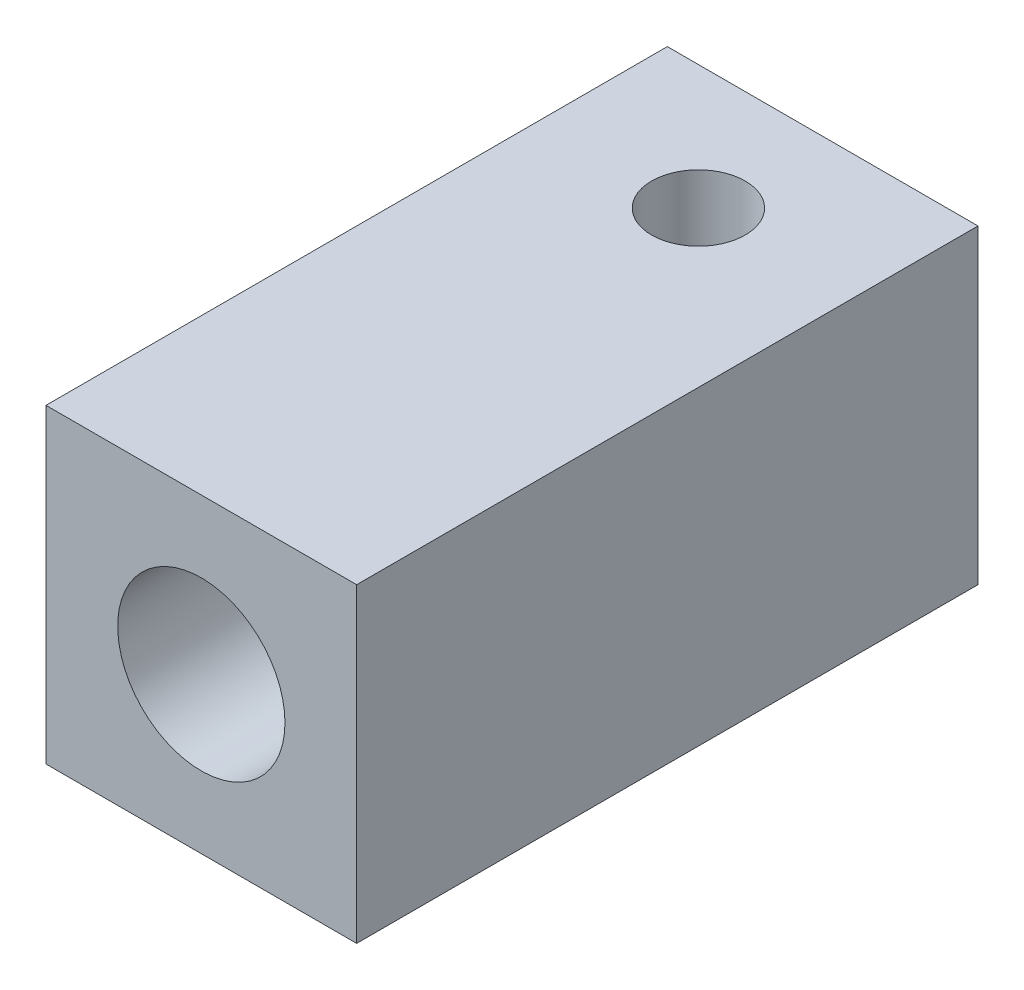
SolidWorks part; units mm, degrees
ref_plane "Front Plane" through (0, 0, 0) normal (0, 0, 1) x (1, 0, 0)
ref_plane "Top Plane" through (0, 0, 0) normal (0, 1, 0) x (1, 0, 0)
ref_plane "Right Plane" through (0, 0, 0) normal (1, 0, 0) x (0, 0, -1)
sketch "Sketch1" plane through (0, 0, 0) normal (0, 0, 1) x (1, 0, 0)
  line L1 (-8.413, 4.7391) -> (-0.913, 4.7391)
  line L2 (-8.413, 4.7391) -> (-8.413, -2.7609)
  line L3 (-8.413, -2.7609) -> (-0.913, -2.7609)
  line L4 (-0.913, 4.7391) -> (-0.913, -2.7609)
  dimension "D1" = 7.5
extrude "Boss-Extrude1" add sketch "Sketch1" along normal blind 15
sketch "10-32 hole for luer screw" plane through (0, 0, 15) normal (0, 0, 1) x (1, 0, 0)
  line L0 (-8.413, 4.7391) -> (-0.913, -2.7609) construction
  circle A0 centre (-4.663, 0.9891) radius 2.0193
  point P4 (-4.663, 0.9891)
  dimension "D1" = 4.0386
sketch "hole for tubing" plane through (0, 0, 0) normal (0, 0, -1) x (-1, 0, 0)
  line L0 (0.913, 4.7391) -> (8.413, -2.7609) construction
  circle A0 centre (4.663, 0.9891) radius 1.1
  point P4 (4.663, 0.9891)
  dimension "D1" = 2.2
extrude "Cut-Extrude1" cut sketch "hole for tubing" against normal through all
extrude "Cut-Extrude2" cut sketch "10-32 hole for luer screw" against normal blind 7.5
sketch "4-40 set screw hole" plane through (0, 4.7391, 0) normal (0, 1, 0) x (1, 0, 0)
  line L0 (-0.913, 0) -> (-8.413, -6) construction
  line L1 (-8.413, -15) -> (-8.413, 0) construction
  circle A0 centre (-4.663, -3) radius 1.1303
  dimension "D2" = 2.2606
  dimension "D1" = 6
extrude "Cut-Extrude3" cut sketch "4-40 set screw hole" against normal blind 2
sketch "Sketch2" plane through (0, 0, 0) normal (0, 0, -1) x (-1, 0, 0)
  line L0 (0.913, -2.7609) -> (8.413, 4.7391) construction
  line L1 (2.7185, -0.9554) -> (6.6076, -0.9554)
  line L2 (2.7185, -0.9554) -> (2.7185, 2.9337)
  line L3 (2.7185, 2.9337) -> (6.6076, 2.9337)
  line L4 (6.6076, -0.9554) -> (6.6076, 2.9337)
  line L5 (6.6076, -0.9554) -> (2.7185, 2.9337) construction
  line L7 (0, -3.9595) -> (7.0377, -3.9595)
  line L8 (0, -3.9595) -> (0, 4.2272)
  line L9 (0, 4.2272) -> (7.0377, 4.2272)
  line L10 (7.0377, -3.9595) -> (7.0377, 4.2272)
  point P8 (4.663, 0.9891)
  point P9 (4.663, 0.9891)
  dimension "D1" = 5.5
extrude "Cut-Extrude4" [suppressed] cut sketch "Sketch2" against normal blind 5
